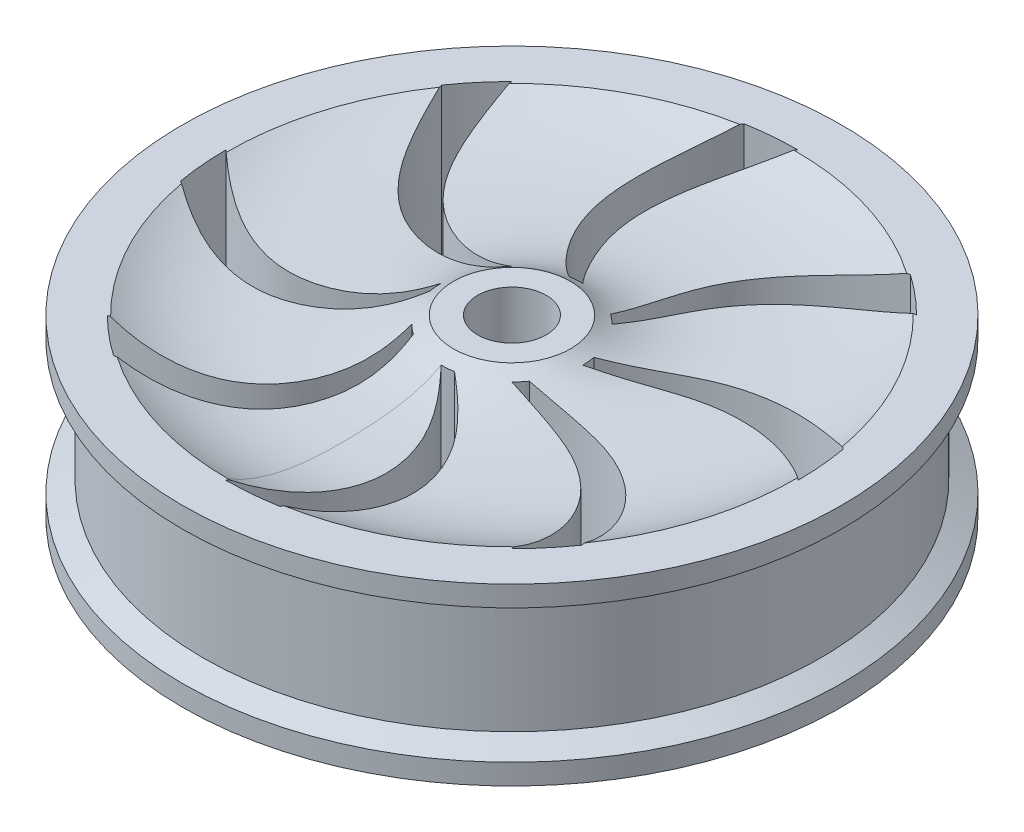
SolidWorks part; units mm, degrees
ref_plane "Front Plane" through (0, 0, 0) normal (0, 0, 1) x (1, 0, 0)
ref_plane "Top Plane" through (0, 0, 0) normal (0, 1, 0) x (1, 0, 0)
ref_plane "Right Plane" through (0, 0, 0) normal (1, 0, 0) x (0, 0, -1)
sketch "Sketch2" plane through (0, 0, 0) normal (0, 0, 1) x (1, 0, 0)
  line L0 (5, 0) -> (48, 0)
  line L1 (55, 0) -> (-55, 0) construction
  line L2 (48, 0) -> (48, 3)
  line L3 (45, 4.7321) -> (48, 3)
  line L4 (45, 4.7321) -> (45, 12.7321)
  line L5 (5, 12.7321) -> (45, 12.7321)
  line L8 (5, 12.7321) -> (5, 0)
  line L9 (0, 23.9449) -> (0, -4.6922) construction
  line L10 (0, -55) -> (0, 55) construction
  dimension "D1" = 5
  dimension "D2" = 45
  dimension "D3" = 3
  dimension "D4" = 8
  dimension "D5" = 60
  dimension "D6" = 3
revolve "Revolve1" add sketch "Sketch2" angle 360 about L9
sketch "Sketch4" plane through (0, 0, 0) normal (0, -1, 0) x (1, 0, 0)
  line L0 (55, 0) -> (-55, 0) construction
  arc A2 (-10.3121, 0) -> (-10.1555, 1.7907) centre (0, 0) cw
  arc A3 (-41.6659, 0) -> (-41.0329, 7.2352) centre (0, 0) cw
  circle A4 centre (0, 0) radius 10.3121 construction
  circle A5 centre (0, 0.5412) radius 41.6694 construction
  spline S0 degree 2 poles (-41.6659, 0) (-25.5457, 14.1944) (-10.3121, 0) knots 0 0 0 1 1 1
  spline S1 degree 2 poles (-41.0329, 7.2352) (-22.6927, 18.4147) (-10.1555, 1.7907) knots 0 0 0 1 1 1
  point P14 (0, 0)
extrude "Cut-Extrude1" cut sketch "Sketch4" against normal blind 20 contours S1 A2 S0 A3
pattern_circular "CirPattern1" count 8 over 360 about axis through (0, 0, 0) along (0, 1, 0) of "Cut-Extrude1"
sketch "Sketch5" plane through (0, 0, 0) normal (0, 0, 1) x (1, 0, 0)
  line L1 (8.5199, 0) -> (41.3335, 0)
  line L2 (0, 22.1828) -> (0, -29.1844) construction
  line L3 (52.8, 0) -> (-52.8, 0) construction
  spline S0 degree 3 poles (8.5199, 0) (12.4733, 2.9519) (23.9609, 4.2016) (35.4178, 3.4908) (41.3335, 0) knots 0 0 0 0 0.416821 1 1 1 1
revolve "Cut-Revolve1" cut sketch "Sketch5" angle 360 about L2
mirror "Mirror1" about plane through (5, 12.7321, 0) normal (0, -1, 0) of bodies 110 106
